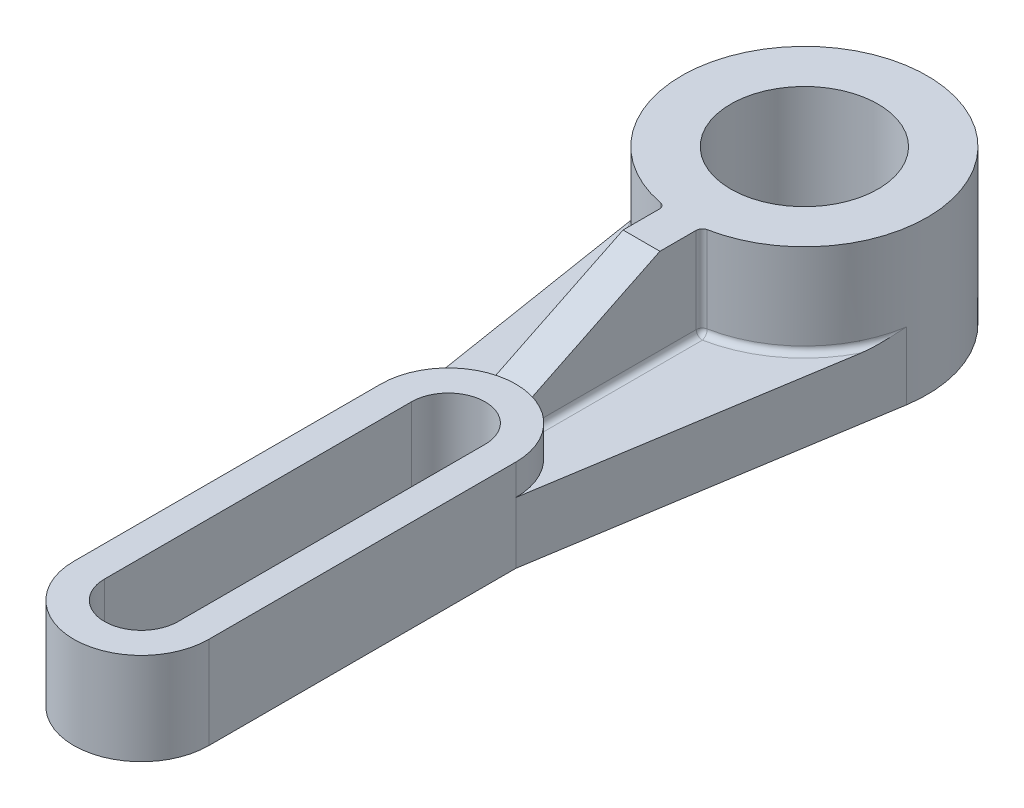
SolidWorks part; units mm, degrees
ref_plane "Ön Düzlem" through (0, 0, 0) normal (0, 0, 1) x (1, 0, 0)
ref_plane "Üst Düzlem" through (0, 0, 0) normal (0, 1, 0) x (1, 0, 0)
ref_plane "Sağ Düzlem" through (0, 0, 0) normal (1, 0, 0) x (0, 0, -1)
sketch "Çizim1" plane through (0, 0, 0) normal (0, 1, 0) x (1, 0, 0)
  line L0 (0, 0) -> (0, -50) construction
  line L1 (11, 0) -> (11, -50)
  line L2 (-11, 0) -> (-11, -50)
  line L3 (11, 0) -> (19.7502, 54.8492)
  line L4 (-11, 0) -> (-19.7502, 54.8492)
  line L5 (6, 0) -> (6, -50)
  line L6 (-6, 0) -> (-6, -50)
  arc A0 (11, 0) -> (-11, 0) centre (0, 0) ccw
  arc A1 (-11, -50) -> (11, -50) centre (0, -50) ccw
  circle A2 centre (0, 58) radius 20
  arc A3 (-6, -50) -> (6, -50) centre (0, -50) ccw
  arc A4 (6, 0) -> (-6, 0) centre (0, 0) ccw
  circle A5 centre (0, 58) radius 12
  point P3 (0, -25)
  dimension "D4" = 24
  dimension "D5" = 40
  dimension "D2" = 22
  dimension "D3" = 50
  dimension "D1" = 12
  dimension "D6" = 58
extrude "Yükseklik-Ekstrüzyon1" add sketch "Çizim1" along normal blind 10 contours L2 A1 L1 A0 A4 L5 A3 L6 | A2 A5 | A2 L4 A0 L3
sketch "Çizim2" plane through (0, 10, 0) normal (0, 1, 0) x (1, 0, 0)
  line L0 (6, 0) -> (6, -50) construction
  line L1 (-6, 0) -> (-6, -50) construction
  line L2 (6, 0) -> (6, -50)
  line L3 (-6, 0) -> (-6, -50)
  line L4 (11, 0) -> (11, -50) construction
  line L5 (-11, 0) -> (-11, -50) construction
  line L6 (11, 0) -> (11, -50)
  line L7 (-11, 0) -> (-11, -50)
  arc A0 (-6, -50) -> (6, -50) centre (0, -50) ccw construction
  arc A1 (6, 0) -> (-6, 0) centre (0, 0) ccw construction
  arc A2 (11, 0) -> (-11, 0) centre (0, 0) ccw construction
  arc A3 (-6, -50) -> (6, -50) centre (0, -50) ccw
  arc A4 (6, 0) -> (-6, 0) centre (0, 0) ccw
  arc A5 (11, 0) -> (-11, 0) centre (0, 0) ccw
  arc A6 (-11, -50) -> (11, -50) centre (0, -50) ccw construction
  arc A7 (-11, -50) -> (11, -50) centre (0, -50) ccw
extrude "Yükseklik-Ekstrüzyon2" add sketch "Çizim2" along normal blind 5
sketch "Çizim3" plane through (0, 10, 0) normal (0, 1, 0) x (1, 0, 0)
  circle A0 centre (0, 58) radius 20 construction
  circle A1 centre (0, 58) radius 20
  circle A2 centre (0, 58) radius 12 construction
  circle A3 centre (0, 58) radius 12
extrude "Yükseklik-Ekstrüzyon3" add sketch "Çizim3" along normal blind 15
sketch "Çizim4" plane through (0, 0, 0) normal (1, 0, 0) x (0, 0, -1)
  line L0 (41.496, 25) -> (31.465, 25)
  line L1 (31.465, 25) -> (9.2036, 14.1222)
  line L3 (9.2036, 14.1222) -> (9.2036, 10)
  line L4 (9.2036, 10) -> (41.496, 10)
  line L6 (41.496, 25) -> (41.496, 10)
  point P3 (0, 0)
  point P11 (0, 0)
  point P12 (0, 0)
  point P13 (0, 0)
  point P14 (0, 0)
extrude "Yükseklik-Ekstrüzyon10" add sketch "Çizim4" along normal mid plane 6
fillet "Radyus1" radius 1 6 edges at (14.0881, 10, -43.804) (-14.0881, 10, -43.804) (3, 10, -24.4046) (3, 17.5, -38.2263) (-3, 17.5, -38.2263) (-3, 10, -24.4046)
